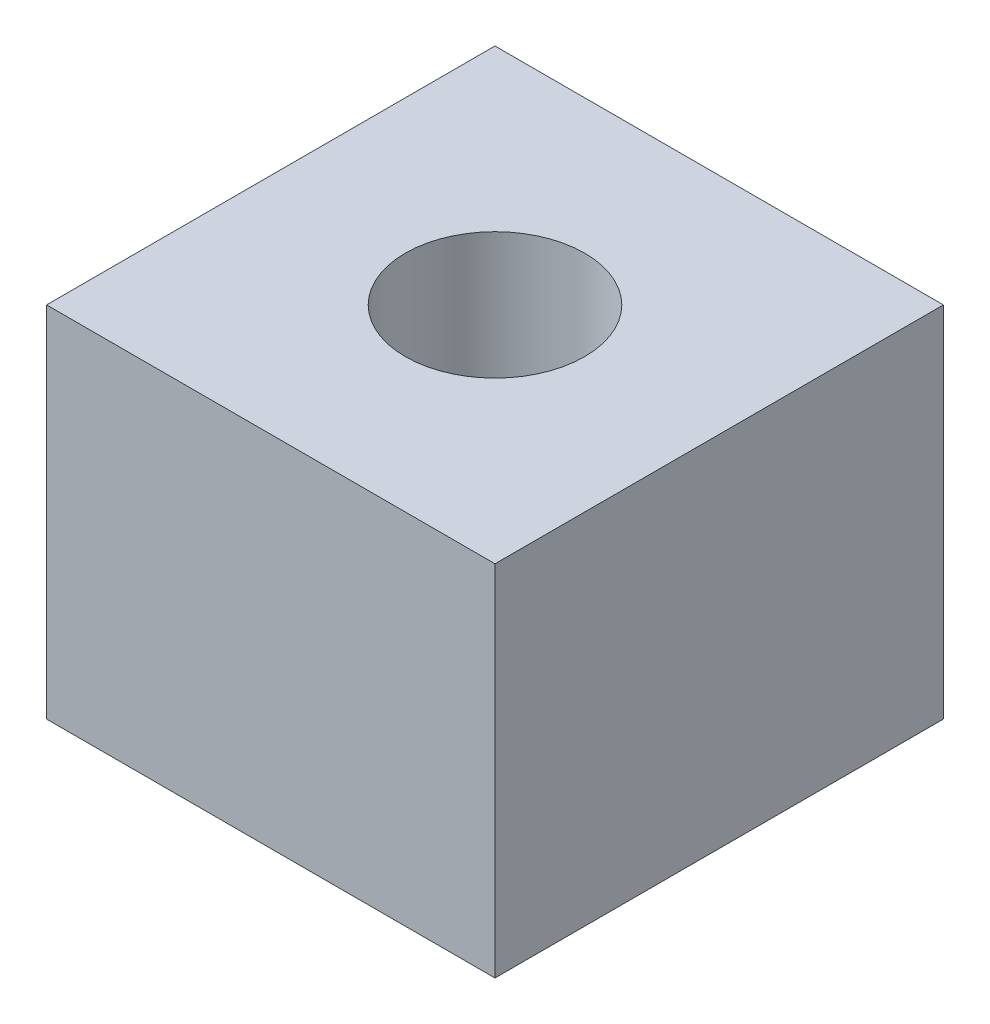
SolidWorks part; units mm, degrees
ref_plane "Front Plane" through (0, 0, 0) normal (0, 0, 1) x (1, 0, 0)
ref_plane "Top Plane" through (0, 0, 0) normal (0, 1, 0) x (1, 0, 0)
ref_plane "Right Plane" through (0, 0, 0) normal (1, 0, 0) x (0, 0, -1)
sketch "Sketch1" plane through (0, 0, 0) normal (0, 1, 0) x (1, 0, 0)
  line L1 (-1.25, -1.25) -> (1.25, -1.25)
  line L2 (-1.25, -1.25) -> (-1.25, 1.25)
  line L3 (-1.25, 1.25) -> (1.25, 1.25)
  line L4 (1.25, -1.25) -> (1.25, 1.25)
  line L5 (-1.25, -1.25) -> (1.25, 1.25) construction
  line L6 (-1.25, 1.25) -> (1.25, -1.25) construction
  point P0 (0, 0)
  dimension "D1" = 2.5
  dimension "D2" = 2.5
extrude "Boss-Extrude1" add sketch "Sketch1" along normal blind 2
sketch "Sketch2" plane through (0, 2, 0) normal (0, 1, 0) x (1, 0, 0)
  circle A0 centre (0, 0) radius 0.5
  dimension "D1" = 1
extrude "Cut-Extrude1" cut sketch "Sketch2" against normal through all both and the other way through all
